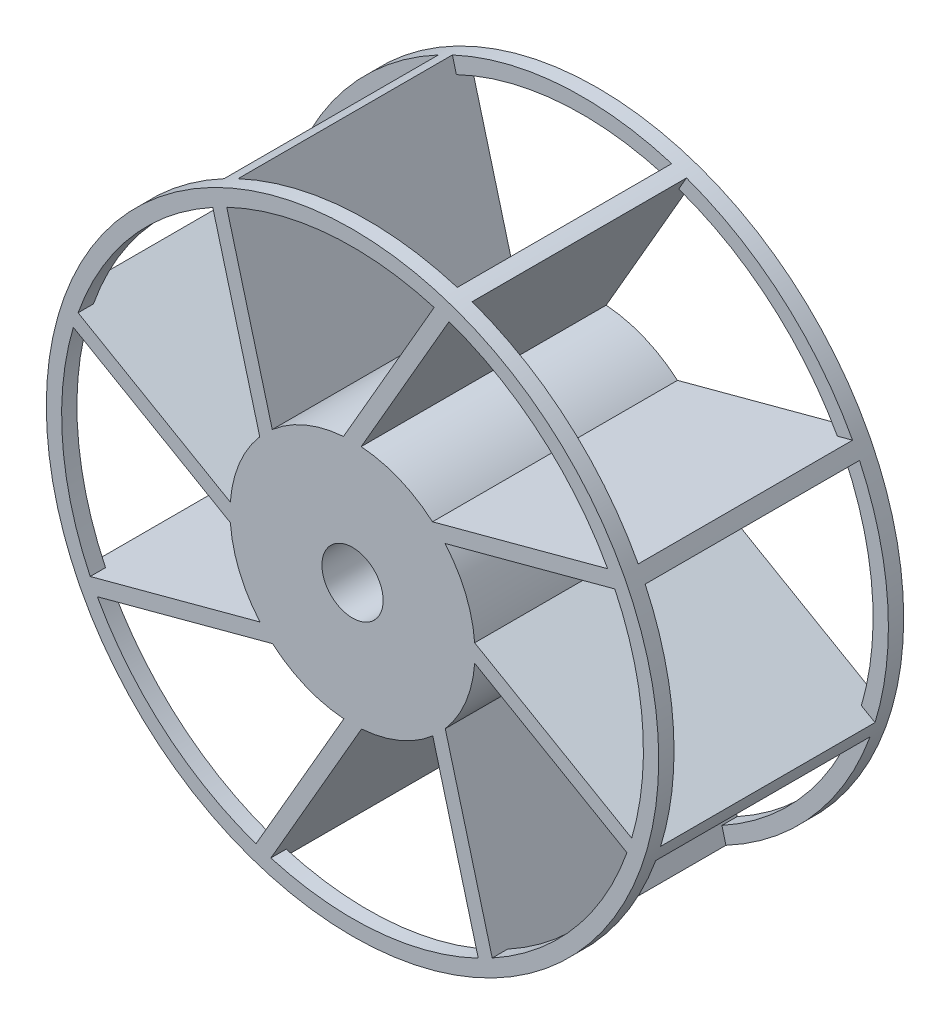
SolidWorks part; units mm, degrees
ref_plane "Front Plane" through (0, 0, 0) normal (0, 0, 1) x (1, 0, 0)
ref_plane "Top Plane" through (0, 0, 0) normal (0, 1, 0) x (1, 0, 0)
ref_plane "Right Plane" through (0, 0, 0) normal (1, 0, 0) x (0, 0, -1)
sketch "Sketch1" plane through (0, 0, 0) normal (0, 0, 1) x (1, 0, 0)
  line L0 (0, 0) -> (127.6133, 0) construction
  line L1 (25.4, 0) -> (60.2315, -20.11) construction
  line L2 (59.7002, -21.6363) -> (25.3364, -1.7964)
  line L3 (60.7263, -18.5626) -> (25.3308, 1.873)
  line L4 (26.9152, -57.5136) -> (16.6453, -19.1858)
  line L5 (29.8143, -56.0657) -> (19.236, -16.5872)
  line L6 (-21.6363, -59.7002) -> (-1.7964, -25.3364)
  line L7 (-18.5626, -60.7263) -> (1.873, -25.3308)
  line L8 (-57.5136, -26.9152) -> (-19.1858, -16.6453)
  line L9 (-56.0657, -29.8143) -> (-16.5872, -19.236)
  line L10 (-59.7002, 21.6363) -> (-25.3364, 1.7964)
  line L11 (-60.7263, 18.5626) -> (-25.3308, -1.873)
  line L12 (-26.9152, 57.5136) -> (-16.6453, 19.1858)
  line L13 (-29.8143, 56.0657) -> (-19.236, 16.5872)
  line L14 (21.6363, 59.7002) -> (1.7964, 25.3364)
  line L15 (18.5626, 60.7263) -> (-1.873, 25.3308)
  line L16 (57.5136, 26.9152) -> (19.1858, 16.6453)
  line L17 (56.0657, 29.8143) -> (16.5872, 19.236)
  arc A0 (59.7002, -21.6363) -> (60.7263, -18.5626) centre (0, 0) ccw
  arc A1 (25.3308, 1.873) -> (25.3364, -1.7964) centre (0, 0) ccw
  arc A2 (19.236, -16.5872) -> (16.6453, -19.1858) centre (0, 0) ccw
  arc A3 (26.9152, -57.5136) -> (29.8143, -56.0657) centre (0, 0) ccw
  arc A4 (1.873, -25.3308) -> (-1.7964, -25.3364) centre (0, 0) ccw
  arc A5 (-21.6363, -59.7002) -> (-18.5626, -60.7263) centre (0, 0) ccw
  arc A6 (-16.5872, -19.236) -> (-19.1858, -16.6453) centre (0, 0) ccw
  arc A7 (-57.5136, -26.9152) -> (-56.0657, -29.8143) centre (0, 0) ccw
  arc A8 (-25.3308, -1.873) -> (-25.3364, 1.7964) centre (0, 0) ccw
  arc A9 (-59.7002, 21.6363) -> (-60.7263, 18.5626) centre (0, 0) ccw
  arc A10 (-19.236, 16.5872) -> (-16.6453, 19.1858) centre (0, 0) ccw
  arc A11 (-26.9152, 57.5136) -> (-29.8143, 56.0657) centre (0, 0) ccw
  arc A12 (-1.873, 25.3308) -> (1.7964, 25.3364) centre (0, 0) ccw
  arc A13 (21.6363, 59.7002) -> (18.5626, 60.7263) centre (0, 0) ccw
  arc A14 (16.5872, 19.236) -> (19.1858, 16.6453) centre (0, 0) ccw
  arc A15 (57.5136, 26.9152) -> (56.0657, 29.8143) centre (0, 0) ccw
  circle A16 centre (0, 0) radius 6.35
  point P40 (0, 0)
  dimension "D1" = 50.8
  dimension "D2" = 127
  dimension "D7" = 12.7
  dimension "D3" = 30
  dimension "D4" = 1.5875
  dimension "D5" = 1.5875
  dimension "D6" = 8
extrude "Boss-Extrude1" add sketch "Sketch1" along normal blind 50.8 contours A1 A2 | L12 A11 L13 A1 | L6 A5 L7 A1 | L4 A3 L5 A1 | L16 A15 L17 A1 | L14 A13 L15 A1 | A2 L2 A0 L3 | L10 A8 L11 A9 | L8 A6 L9 A7 region at (42.8029, -10.0386, 0) region at (22.8171, -9.4107, 0) region at (23.1679, -37.3646, 0) region at (37.3646, 23.1679, 0) region at (-10.0386, -42.8029, 0) region at (10.0386, 42.8029, 0) region at (-23.1679, 37.3646, 0)
sketch "Sketch2" plane through (0, 0, 50.8) normal (0, 0, 1) x (1, 0, 0)
  circle A0 centre (0, 0) radius 63.5
  circle A1 centre (0, 0) radius 60.325
  dimension "D1" = 120.65
  dimension "D2" = 127
extrude "Boss-Extrude2" add sketch "Sketch2" against normal blind 3.175
sketch "Sketch6" plane through (0, 0, 0) normal (0, 0, -1) x (-1, 0, 0)
  circle A0 centre (0, 0) radius 63.5 construction
  circle A1 centre (0, 0) radius 60.325 construction
  circle A2 centre (0, 0) radius 63.5
  circle A3 centre (0, 0) radius 60.325
extrude "Boss-Extrude3" add sketch "Sketch6" against normal blind 3.175
extrude "Cut-Extrude1" cut sketch "Sketch1<3>" along normal up to surface (50.8 mm away) contours A16 up to face at (-23.599, -33.671, 50.8)
sketch "Sketch1<3>" plane through (0, 0, 0) normal (0, 0, 1) x (1, 0, 0) same geometry as "Sketch1"
